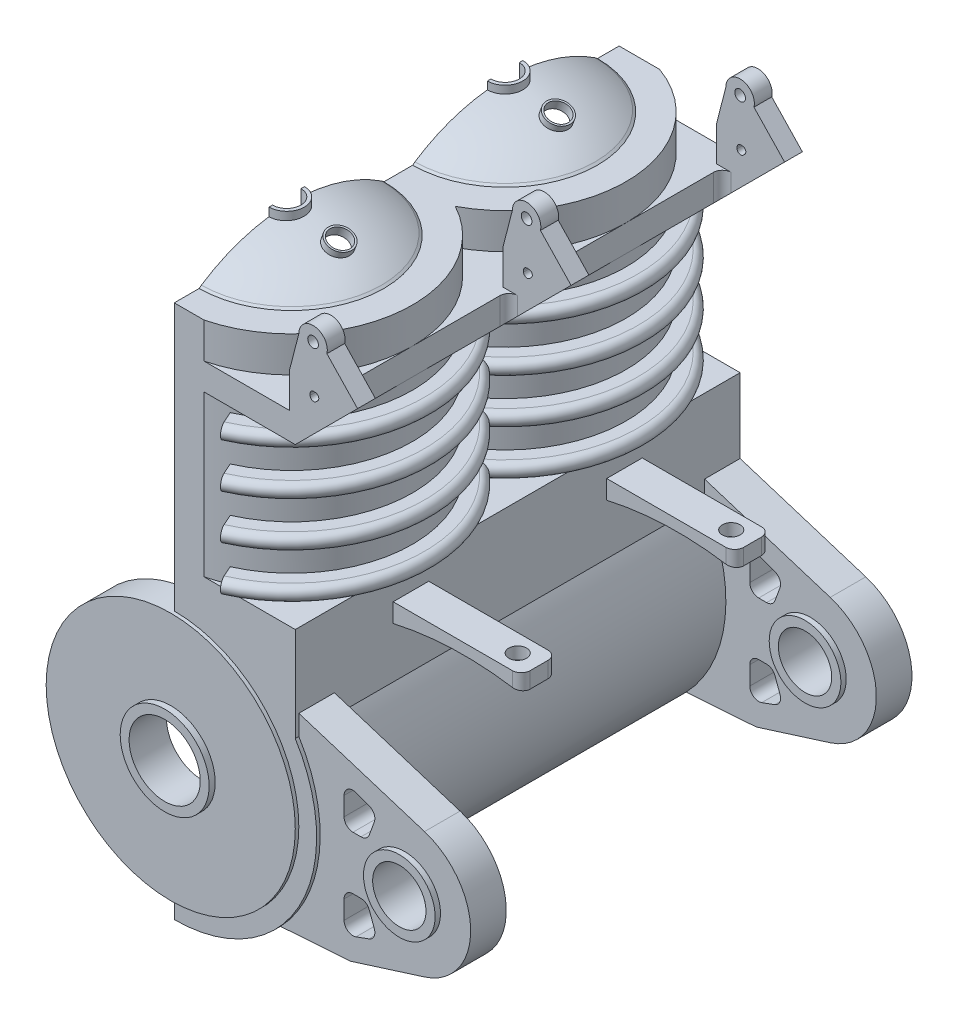
SolidWorks part; units mm, degrees
ref_plane "Front Plane" through (0, 0, 0) normal (0, 0, 1) x (1, 0, 0)
ref_plane "Top Plane" through (0, 0, 0) normal (0, 1, 0) x (1, 0, 0)
ref_plane "Right Plane" through (0, 0, 0) normal (1, 0, 0) x (0, 0, -1)
sketch "Sketch6" plane through (0, 0, 0) normal (0, 0, 1) x (1, 0, 0)
  line L0 (-15.966, -15.2438) -> (-15.966, 12.7762)
  line L1 (-15.966, 12.7762) -> (-9.166, 12.7762)
  line L2 (-9.166, 12.7762) -> (-9.166, -3.0296)
  arc A0 (-15.966, -15.2438) -> (-9.166, -3.0296) centre (-15.966, -7.2438) ccw
  dimension "D1" = 16
  dimension "D2" = 28.02
  dimension "D3" = 6.8
extrude "Boss-Extrude1" add sketch "Sketch6" along normal blind 25
sketch "Sketch7" plane through (0, 12.7762, 0) normal (0, 1, 0) x (1, 0, 0)
  line L0 (-15.966, -25) -> (-15.966, 0) construction
  circle A0 centre (-15.966, -6.41) radius 5
  circle A1 centre (-15.966, -18.41) radius 5
  point P6 (0, 0)
  dimension "D2" = 10
  dimension "D1" = 12
  dimension "D3" = 6.59
extrude "Cut-Extrude1" cut sketch "Sketch7" against normal blind 20
sketch "Sketch8" plane through (0, 0, 25) normal (0, 0, 1) x (1, 0, 0)
  circle A0 centre (-15.966, -7.2238) radius 7
  dimension "D1" = 14
extrude "Cut-Extrude3" cut sketch "Sketch8" against normal blind 30
ref_plane "Plane1" through (0, 11.2762, 0) normal (0, 1, 0) x (1, 0, 0)
sketch "Sketch9" plane through (0, 11.2762, 0) normal (0, 1, 0) x (1, 0, 0)
  line L0 (-15.966, 0.39) -> (-5.2398, 0.39)
  line L1 (-5.2398, 0.39) -> (-5.2398, -25.21)
  line L2 (-5.2398, -25.21) -> (-15.966, -25.21)
  arc A5 (-15.966, -13.21) -> (-15.966, 0.39) centre (-15.966, -6.41) ccw
  arc A6 (-12.766, -12.41) -> (-15.966, 0.39) centre (-15.966, -6.41) ccw
  arc A8 (-15.966, -25.21) -> (-15.966, -11.61) centre (-15.966, -18.41) ccw
  arc A9 (-15.966, -25.21) -> (-12.766, -12.41) centre (-15.966, -18.41) ccw
  dimension "D1" = 1.8
  dimension "D2" = 1.8
extrude "Cut-Extrude4" cut sketch "Sketch9" against normal blind 9
sketch "Sketch10" plane through (-15.966, 0, 0) normal (-1, 0, 0) x (0, 0, 1)
  line L0 (1.41, 12.7762) -> (0, 12.7762) construction
  line L1 (0.175, 11.9262) -> (0.68, 11.9262)
  line L2 (0.175, 11.9262) -> (0.175, 1.9262)
  line L3 (0.175, 1.9262) -> (0.68, 1.9262)
  line L4 (0.68, 11.9262) -> (0.68, 1.9262)
  line L5 (0, 12.7762) -> (0, -0.2238) construction
  line L6 (6.41, 12.7762) -> (6.41, -2.3249) construction
  line L7 (0.175, 10.6262) -> (-1.07, 10.6262)
  line L8 (0.175, 10.6262) -> (0.175, 9.8262)
  line L9 (0.175, 9.8262) -> (-1.07, 9.8262)
  line L11 (0.175, 8.1262) -> (-1.07, 8.1262)
  line L12 (0.175, 8.1262) -> (0.175, 7.3262)
  line L13 (0.175, 7.3262) -> (-1.07, 7.3262)
  line L15 (0.175, 5.6262) -> (-1.07, 5.6262)
  line L16 (0.175, 5.6262) -> (0.175, 4.8262)
  line L17 (0.175, 4.8262) -> (-1.07, 4.8262)
  line L19 (0.175, 3.1262) -> (-1.07, 3.1262)
  line L20 (0.175, 3.1262) -> (0.175, 2.3262)
  line L21 (0.175, 2.3262) -> (-1.07, 2.3262)
  line L23 (11.41, 12.7762) -> (1.41, 12.7762) construction
  arc A0 (-1.07, 3.1262) -> (-1.07, 2.3262) centre (-1.07, 2.7262) ccw
  arc A1 (-1.07, 5.6262) -> (-1.07, 4.8262) centre (-1.07, 5.2262) ccw
  arc A2 (-1.07, 8.1262) -> (-1.07, 7.3262) centre (-1.07, 7.7262) ccw
  arc A3 (-1.07, 10.6262) -> (-1.07, 9.8262) centre (-1.07, 10.2262) ccw
  spline S0 degree 2 poles (11.41, -0.2238) (6.41, -3.7953) (1.41, -0.2238) knots 0 0 0 1 1 1 weights 0.002 0.007 0.012 construction
  dimension "D1" = 10
  dimension "D2" = 0.505
  dimension "D3" = 0.85
  dimension "D4" = 0.68
  dimension "D6" = 0.8
  dimension "D7" = 2.15
  dimension "D8" = 2.5
  dimension "D9" = 2.5
  dimension "D10" = 2.5
revolve "Revolve4" add sketch "Sketch10" angle 156 about L6 region at (-15.966, 6.9262, 0.4275) region at (-15.966, 10.2262, 0.0875) region at (-15.966, 10.2262, -0.695) region at (-15.966, 7.7262, 0.0875) region at (-15.966, 2.7262, 0.0875) region at (-15.966, 7.7262, -0.695) region at (-15.966, 2.7262, -0.695) region at (-15.966, 5.2262, 0.0875) region at (-15.966, 5.2262, -0.695)
pattern_linear "LPattern1" count 2 spacing 12 along (0, 0, 1) of "Revolve4"
sketch "Sketch11" plane through (0, 12.7762, 0) normal (0, 1, 0) x (1, 0, 0)
  circle A0 centre (-15.966, -6.41) radius 5
extrude "Cut-Extrude5" cut sketch "Sketch11" against normal blind 15
sketch "Sketch12" plane through (0, 0, 0) normal (0, 0, -1) x (-1, 0, 0)
  circle A0 centre (15.966, -7.2238) radius 7
  circle A1 centre (15.966, -7.2238) radius 2.5
  dimension "D1" = 5
  dimension "D2" = 14
extrude "Boss-Extrude2" add sketch "Sketch12" along normal blind 0.5 and the other way blind 1
pattern_linear "LPattern2" count 3 spacing 12 along (0, 0, 1) of "Boss-Extrude2"
sketch "Sketch13" plane through (0, 0, 25) normal (0, 0, 1) x (1, 0, 0)
  circle A0 centre (-15.966, -7.2238) radius 2.5 construction
  circle A1 centre (-15.966, -7.2238) radius 2.5
  arc A2 (-15.966, -14.2238) -> (-15.966, -0.2238) centre (-15.966, -7.2238) ccw construction
  arc A3 (-15.966, -14.2238) -> (-15.966, -0.2238) centre (-15.966, -7.2238) ccw
  arc M8 (-15.966, -0.2238) -> (-15.966, -14.2238) centre (-15.966, -7.2238) ccw
  circle M11 centre (-15.966, -7.2238) radius 2.5
extrude "Boss-Extrude3" add sketch "Sketch13" along normal blind 0.2 contours A3 M8 M11 region at (-22.768, -7.2238, 25)
sketch "Sketch14" plane through (0, 0, -0.5) normal (0, 0, -1) x (-1, 0, 0)
  circle A0 centre (15.966, -7.2238) radius 2.5 construction
  circle A1 centre (15.966, -7.2238) radius 2.5
  circle A2 centre (15.966, -7.2238) radius 2
  dimension "D1" = 4
extrude "Boss-Extrude4" add sketch "Sketch14" along normal blind 0.5 and the other way blind 1.6
pattern_linear "LPattern4" count 3 spacing 12.22 along (0, 0, 1) of "Boss-Extrude4"
sketch "Sketch15" plane through (0, 12.7762, 0) normal (0, 1, 0) x (1, 0, 0)
  line L0 (-13.6962, 0) -> (-15.966, 0)
  line L1 (-14.2891, -25) -> (-15.966, -25)
  line L2 (-15.966, -25) -> (-15.966, -23.41)
  line L6 (-15.966, 0) -> (-15.966, -1.41)
  line L7 (-15.966, -11.41) -> (-15.966, -13.41)
  line L8 (-15.966, -23.41) -> (-15.966, -25)
  line L9 (-15.966, -25) -> (-9.166, -25)
  line L10 (-9.166, -25) -> (-9.166, 0)
  line L11 (-9.166, 0) -> (-15.966, 0)
  line L12 (-15.966, 0) -> (-15.966, -1.41)
  line L13 (-15.966, -11.41) -> (-15.966, -13.41)
  line L14 (-15.966, -23.41) -> (-15.966, -25)
  line L15 (-15.966, -25) -> (-9.166, -25)
  line L16 (-9.166, -25) -> (-9.166, 0)
  line L17 (-9.166, 0) -> (-15.966, 0)
  arc A0 (-14.2891, -25) -> (-9.166, -18.41) centre (-15.966, -18.41) ccw construction
  arc A1 (-9.166, -6.41) -> (-13.6962, 0) centre (-15.966, -6.41) ccw construction
  arc A2 (-15.966, -11.41) -> (-15.966, -1.41) centre (-15.966, -6.41) ccw
  arc A3 (-15.966, -23.41) -> (-15.966, -13.41) centre (-15.966, -18.41) ccw
  arc A4 (-15.966, -11.41) -> (-15.966, -1.41) centre (-15.966, -6.41) ccw
  arc A5 (-15.966, -23.41) -> (-15.966, -13.41) centre (-15.966, -18.41) ccw
  arc A6 (-12.766, -12.41) -> (-9.166, -6.41) centre (-15.966, -6.41) ccw construction
  arc A7 (-9.166, -18.41) -> (-12.766, -12.41) centre (-15.966, -18.41) ccw construction
  arc A8 (-14.2891, -25) -> (-9.166, -18.41) centre (-15.966, -18.41) ccw
  arc A9 (-9.166, -6.41) -> (-13.6962, 0) centre (-15.966, -6.41) ccw
  arc A10 (-12.766, -12.41) -> (-9.166, -6.41) centre (-15.966, -6.41) ccw
  arc A11 (-9.166, -18.41) -> (-12.766, -12.41) centre (-15.966, -18.41) ccw
  line M9 (-15.966, 0) -> (-15.966, -1.41)
  arc M10 (-15.966, -1.41) -> (-15.966, -11.41) centre (-15.966, -6.41) cw
  line M11 (-15.966, -11.41) -> (-15.966, -13.41)
  arc M12 (-15.966, -13.41) -> (-15.966, -23.41) centre (-15.966, -18.41) cw
  line M13 (-15.966, -23.41) -> (-15.966, -25)
  line M14 (-15.966, -25) -> (-9.166, -25)
  line M16 (-9.166, 0) -> (-15.966, 0)
  dimension "D1" = 0
extrude "Boss-Extrude5" add sketch "Sketch15" along normal blind 2 contours A8 A11 A10 A9 M16 M9 M10 M11 M12 M13 M14 region at (-10.6245, 12.7762, 2.6349)
sketch "Sketch16" plane through (0, 0, 0) normal (0, 0, -1) x (-1, 0, 0)
  line L0 (15.966, -7.2238) -> (-4.9526, -7.2238) construction
  line L1 (3.219, -7.6663) -> (7.061, -7.6663) construction
  line L2 (9.166, -1.9012) -> (2.1033, -4.1281)
  line L3 (9.166, -3.0296) -> (9.166, 2.2762) construction
  line L5 (6.2564, -12.5141) -> (10.1997, -12.789)
  line L6 (9.166, -3.0296) -> (9.166, -1.9012)
  line L7 (2.1033, -11.2046) -> (6.2564, -12.5141)
  circle A0 centre (3.219, -7.6663) radius 2.013
  arc A1 (2.1033, -11.2046) -> (2.1033, -4.1281) centre (3.219, -7.6663) cw
  arc A2 (9.166, -3.0296) -> (15.966, -15.2438) centre (15.966, -7.2438) ccw construction
  arc A3 (9.166, -3.0296) -> (10.1997, -12.789) centre (15.966, -7.2438) ccw
  point P12 (7.6549, -11.9049)
  point P16 (9.4641, -11.9049)
  point P18 (0, 0)
  point P19 (3.7721, -4.5505)
  point P20 (3.7721, -4.5505)
  point P21 (3.7721, -4.5505)
  point P22 (3.7721, -4.5505)
  point P23 (9.166, -2.0838)
  point P24 (6.4672, -11.3763)
  point P25 (2.4311, -4.0179)
  point P26 (2.4311, -4.0179)
  point P27 (2.4311, -4.0179)
  point P28 (4.0841, -10.5568)
  point P29 (0, 0)
  point P30 (4.0919, -11.9049)
  point P31 (7.061, -11.9049)
  point P32 (10.1997, -12.789)
  dimension "D1" = 4.026
  dimension "D4" = 0
  dimension "D5" = 3.71
  dimension "D2" = 0.4425
  dimension "D6" = 35
extrude "Boss-Extrude6" add sketch "Sketch16" against normal blind 2
pattern_linear "LPattern5" count 2 spacing 22.8 along (0, 0, 1) of "Boss-Extrude6"
sketch "Sketch17" plane through (0, 0, 0) normal (0, 0, -1) x (-1, 0, 0)
  circle A0 centre (3.219, -7.6663) radius 2.013 construction
  circle A1 centre (3.219, -7.6663) radius 2.013
  circle A2 centre (3.219, -7.6663) radius 1.5
  dimension "D1" = 3
extrude "Boss-Extrude7" add sketch "Sketch17" along normal blind 0.3 and the other way blind 2.3
pattern_linear "LPattern7" count 2 spacing 22.8 along (0, 0, 1) of "Boss-Extrude7"
sketch "Sketch18" plane through (0, 0, 0) normal (0, 0, -1) x (-1, 0, 0)
  line L0 (5.9521, -4.1568) -> (5.2206, -4.4244)
  line L1 (4.9228, -5.0658) -> (5.2061, -5.8402)
  line L2 (5.6757, -6.1684) -> (6.1239, -6.1684)
  line L3 (6.6239, -5.6684) -> (6.6239, -4.6264)
  line L5 (6.6239, -9.6643) -> (6.6239, -10.7063)
  line L6 (5.6757, -9.1643) -> (6.1239, -9.1643)
  line L7 (4.9228, -10.2669) -> (5.2061, -9.4925)
  line L8 (5.9521, -11.1759) -> (5.2206, -10.9083)
  arc A0 (6.6239, -5.6684) -> (6.1239, -6.1684) centre (6.1239, -5.6684) cw
  arc A1 (5.6757, -6.1684) -> (5.2061, -5.8402) centre (5.6757, -5.6684) cw
  arc A2 (4.9228, -5.0658) -> (5.2206, -4.4244) centre (5.3924, -4.894) cw
  arc A3 (5.9521, -4.1568) -> (6.6239, -4.6264) centre (6.1239, -4.6264) cw
  arc A4 (6.6239, -9.6643) -> (6.1239, -9.1643) centre (6.1239, -9.6643) ccw
  arc A5 (5.6757, -9.1643) -> (5.2061, -9.4925) centre (5.6757, -9.6643) ccw
  arc A6 (4.9228, -10.2669) -> (5.2206, -10.9083) centre (5.3924, -10.4387) ccw
  arc A7 (5.9521, -11.1759) -> (6.6239, -10.7063) centre (6.1239, -10.7063) ccw
  dimension "D1" = 0.5
extrude "Cut-Extrude7" cut sketch "Sketch18" against normal through all
sketch "Sketch20" plane through (-15.966, 0, 0) normal (-1, 0, 0) x (0, 0, 1)
  line L0 (18.41, 14.7762) -> (18.41, 6.2762) construction
  line L1 (23.41, 14.7762) -> (13.41, 14.7762) construction
  line L2 (18.41, 16.3962) -> (18.41, 16.2762)
  line L4 (11.41, 14.7762) -> (13.41, 14.7762) construction
  line L5 (13.2172, 14.7762) -> (13.3439, 14.8763)
  line L6 (13.2172, 14.7762) -> (13.41, 14.7762)
  line L7 (13.2172, 14.7762) -> (13.41, 14.7762)
  line L8 (13.2172, 14.7762) -> (13.41, 14.7762)
  arc A0 (13.41, 14.7762) -> (18.41, 16.2762) centre (18.41, 7.1928) cw
  arc A1 (13.3439, 14.8763) -> (18.41, 16.3962) centre (18.41, 7.1928) cw
  dimension "D1" = 8.5
  dimension "D2" = 10
  dimension "D3" = 0.12
revolve "Revolve6" add sketch "Sketch20" angle 180 about L0 region at (-15.966, 16.3362, 18.3556)
pattern_linear "LPattern8" count 2 spacing 12 along (0, 0, -1) of "Revolve6"
sketch "Sketch22" plane through (0, 14.7762, 0) normal (0, 1, 0) x (1, 0, 0)
  line L0 (-15.966, -1.3439) -> (-15.966, -11.4761) construction
  line L1 (-15.966, -13.3439) -> (-15.966, -23.4761) construction
  circle A0 centre (-15.966, -6.41) radius 0.995
  circle A1 centre (-15.966, -18.6826) radius 0.995
  dimension "D1" = 1.99
  dimension "D2" = 1.99
extrude "Cut-Extrude8" cut sketch "Sketch22" along normal through all
sketch "Sketch23" plane through (0, 14.7762, 0) normal (0, 1, 0) x (1, 0, 0)
  line L2 (-15.966, -5.415) -> (-15.966, -5.61)
  line L3 (-15.966, -7.21) -> (-15.966, -7.405)
  line L4 (-15.966, -17.6876) -> (-15.966, -17.8826)
  line L5 (-15.966, -19.4826) -> (-15.966, -19.6776)
  arc A0 (-15.966, -7.405) -> (-15.966, -5.415) centre (-15.966, -6.41) ccw construction
  arc A1 (-15.966, -7.405) -> (-15.966, -5.415) centre (-15.966, -6.41) ccw
  arc A2 (-15.966, -19.6776) -> (-15.966, -17.6876) centre (-15.966, -18.6826) ccw construction
  arc A3 (-15.966, -19.6776) -> (-15.966, -17.6876) centre (-15.966, -18.6826) ccw
  arc A4 (-15.966, -19.4826) -> (-15.966, -17.8826) centre (-15.966, -18.6826) ccw
  arc A5 (-15.966, -7.21) -> (-15.966, -5.61) centre (-15.966, -6.41) ccw
  dimension "D1" = 1.6
  dimension "D2" = 1.6
extrude "Boss-Extrude8" add sketch "Sketch23" along normal blind 0.8 from offset 1.2
ref_plane "Plane2" through (2.8813, 7.9163, 0) normal (0.342, 0.9397, 0) x (0, 0, 1)
sketch "Sketch24" plane through (2.8813, 7.9163, 0) normal (0.342, 0.9397, 0) x (0, 0, 1)
  line L0 (6.41, -19.3729) -> (6.41, -14.208) construction
  line L1 (6.41, -20.7409) -> (6.41, -17.7409) construction
  line L2 (18.6826, -20.7409) -> (18.6826, -17.7409) construction
  circle A0 centre (6.41, -17.7409) radius 0.6
  circle A1 centre (18.6826, -17.7409) radius 0.6
  point P8 (0, 0)
  point P9 (0, 0)
  point P10 (0, 0)
  point P11 (0, 0)
  point P12 (0, 0)
  point P13 (0, 0)
  point P14 (0, 0)
  point P15 (0, 0)
  point P16 (0, 0)
  dimension "D1" = 1.2
  dimension "D2" = 1.2
  dimension "D3" = 3
  dimension "D4" = 3
extrude "Cut-Extrude9" cut sketch "Sketch24" along normal through all
sketch "Sketch25" plane through (0, 0, 0) normal (0, 0, -1) x (-1, 0, 0)
  line L0 (9.166, 11.2762) -> (9.481, 11.2762)
  line L1 (9.166, 11.2762) -> (13.6962, 11.2762) construction
  line L2 (9.481, 11.2762) -> (9.481, 14.7762)
  line L3 (13.6962, 14.7762) -> (9.166, 14.7762) construction
  line L4 (9.481, 14.7762) -> (7.166, 14.7762)
  line L5 (7.166, 14.7762) -> (6.0417, 15.9005)
  line L7 (5.2917, 15.1505) -> (9.166, 11.2762)
  line L8 (7.9043, 14.0378) -> (7.9931, 13.9491)
  line L9 (8.3345, 14.0905) -> (8.3345, 14.1793)
  line L10 (8.1345, 14.3793) -> (8.0458, 14.3793)
  arc A0 (6.0417, 15.9005) -> (5.2917, 15.1505) centre (5.6667, 15.5255) ccw
  circle A1 centre (5.6667, 15.5255) radius 0.3
  arc A2 (8.0458, 14.3793) -> (7.9043, 14.0378) centre (8.0458, 14.1793) ccw
  arc A3 (7.9931, 13.9491) -> (8.3345, 14.0905) centre (8.1345, 14.0905) ccw
  arc A4 (8.3345, 14.1793) -> (8.1345, 14.3793) centre (8.1345, 14.1793) ccw
  point P15 (8.3441, 13.6076)
  dimension "D5" = 0.6
  dimension "D6" = 1.0607
  dimension "D7" = 0.2
  dimension "D1" = 135
  dimension "D2" = 0.315
  dimension "D3" = 2.315
  dimension "D4" = 1.59
extrude "Boss-Extrude9" add sketch "Sketch25" against normal blind 1
pattern_linear "LPattern9" count 3 spacing 12 along (0, 0, 1) of "Boss-Extrude9"
fillet "Fillet1" radius 0.5 2 edges at (-9.166, 12.0262, 24) (-9.166, 12.0262, 12)
fillet "Fillet2" radius 0.5 2 edges at (-9.166, 12.0262, 1) (-9.166, 12.0262, 13)
sketch "Sketch26" plane through (0, 0, 0) normal (0, 0, -1) x (-1, 0, 0)
  line L0 (9.166, 0.8762) -> (1.966, 0.8762)
  line L1 (9.166, -1.9012) -> (9.166, 2.2762) construction
  line L2 (1.966, 0.8762) -> (1.966, -0.0238)
  line L12 (9.166, 2.2762) -> (9.166, -1.9012)
  line L13 (9.166, -1.9012) -> (2.1033, -4.1281)
  line L14 (2.1033, -11.2046) -> (6.2564, -12.5141)
  line L15 (6.2564, -12.5141) -> (10.1997, -12.789)
  line L16 (15.966, -15.2438) -> (15.966, -14.2238)
  line L17 (15.966, -0.2238) -> (15.966, 2.3262)
  line L18 (15.966, 2.3262) -> (13.6962, 2.3262)
  line L19 (13.6962, 2.3262) -> (13.6962, 2.2762)
  line L20 (13.6962, 2.2762) -> (9.166, 2.2762)
  line L21 (9.166, 0.8762) -> (9.166, -0.1805)
  arc A0 (1.966, -0.0238) -> (9.166, -0.1805) centre (5.1839, -17.6627) cw
  circle A1 centre (15.966, -7.2238) radius 2 construction
  arc A5 (2.1033, -4.1281) -> (2.1033, -11.2046) centre (3.219, -7.6663) ccw
  arc A6 (10.1997, -12.789) -> (15.966, -15.2438) centre (15.966, -7.2438) ccw
  arc A7 (15.966, -0.2238) -> (15.966, -14.2238) centre (15.966, -7.2238) ccw
  dimension "D4" = 17.93
  dimension "D1" = 8.1
  dimension "D2" = 0.9
  dimension "D3" = 7.2
  dimension "D5" = 0
extrude "Boss-Extrude10" add sketch "Sketch26" against normal blind 2 from offset 5.5 offset against normal yes
pattern_linear "LPattern10" count 2 spacing 12 along (0, 0, 1) of "Boss-Extrude10"
sketch "Sketch27" plane through (0, 0.8762, 0) normal (0, 1, 0) x (1, 0, 0)
  line L0 (-1.966, -7.5) -> (-1.966, -5.5) construction
  line L1 (-1.966, -19.5) -> (-1.966, -17.5) construction
  circle A0 centre (-3.166, -6.5) radius 0.5
  circle A1 centre (-3.166, -18.5) radius 0.5
  point P6 (0, 0)
  point P7 (-1.966, -6.5)
  point P10 (-1.966, -18.5)
  dimension "D1" = 1
  dimension "D4" = 1
  dimension "D2" = 1.2
  dimension "D3" = 1.2
extrude "Cut-Extrude10" cut sketch "Sketch27" along normal mid plane 5
fillet "Fillet3" radius 0.5 4 edges at (-1.966, 0.4262, 5.5) (-1.966, 0.4262, 7.5) (-1.966, 0.4262, 19.5) (-1.966, 0.4262, 17.5)
sketch "Sketch28" plane through (0, 0, 0) normal (0, 0, -1) x (-1, 0, 0)
  line L0 (9.481, 14.7762) -> (7.166, 14.7762) construction
  line L1 (2.9673, 17.3201) -> (7.3144, 17.3201)
  line L2 (2.9673, 17.3201) -> (2.9673, 14.7762)
  line L3 (2.9673, 14.7762) -> (7.3144, 14.7762)
  line L4 (7.3144, 17.3201) -> (7.3144, 14.7762)
extrude "Cut-Extrude11" cut sketch "Sketch28" against normal through all
sketch "Sketch29" plane through (0, 0, 0) normal (0, 0, -1) x (-1, 0, 0)
  line L0 (9.481, 14.7762) -> (8.966, 16.7762)
  line L1 (7.3885, 16.5877) -> (5.666, 14.7762)
  line L2 (5.666, 14.7762) -> (9.166, 11.2762) construction
  line L3 (9.481, 14.7762) -> (5.666, 14.7762) construction
  line L4 (15.966, 16.7762) -> (15.966, 16.3422) construction
  circle A0 centre (8.166, 16.7762) radius 0.3
  arc A1 (8.966, 16.7762) -> (7.3885, 16.5877) centre (8.166, 16.7762) ccw
  point P5 (0, 0)
  point P12 (0, 0)
  line M1 (9.481, 14.7762) -> (5.666, 14.7762)
  dimension "D3" = 0.6
  dimension "D4" = 0.8
  dimension "D1" = 7.8
  dimension "D2" = 2
extrude "Boss-Extrude11" add sketch "Sketch29" against normal blind 1 contours L0 A1 L1 A0 M1 region at (-7.9015, 15.8226, 0)
pattern_linear "LPattern11" count 3 spacing 12 along (0, 0, 1) of "Boss-Extrude11"
sketch "Sketch31" plane through (2.8813, 7.9163, 0) normal (0.342, 0.9397, 0) x (0, 0, 1)
  circle A0 centre (6.41, -17.7409) radius 0.6
  circle A1 centre (18.6826, -17.7409) radius 0.6
extrude "Extrude-Thin1" add sketch "Sketch31" along normal blind 0.5 from offset 1.9 thin thin type one direction wall 0.1
